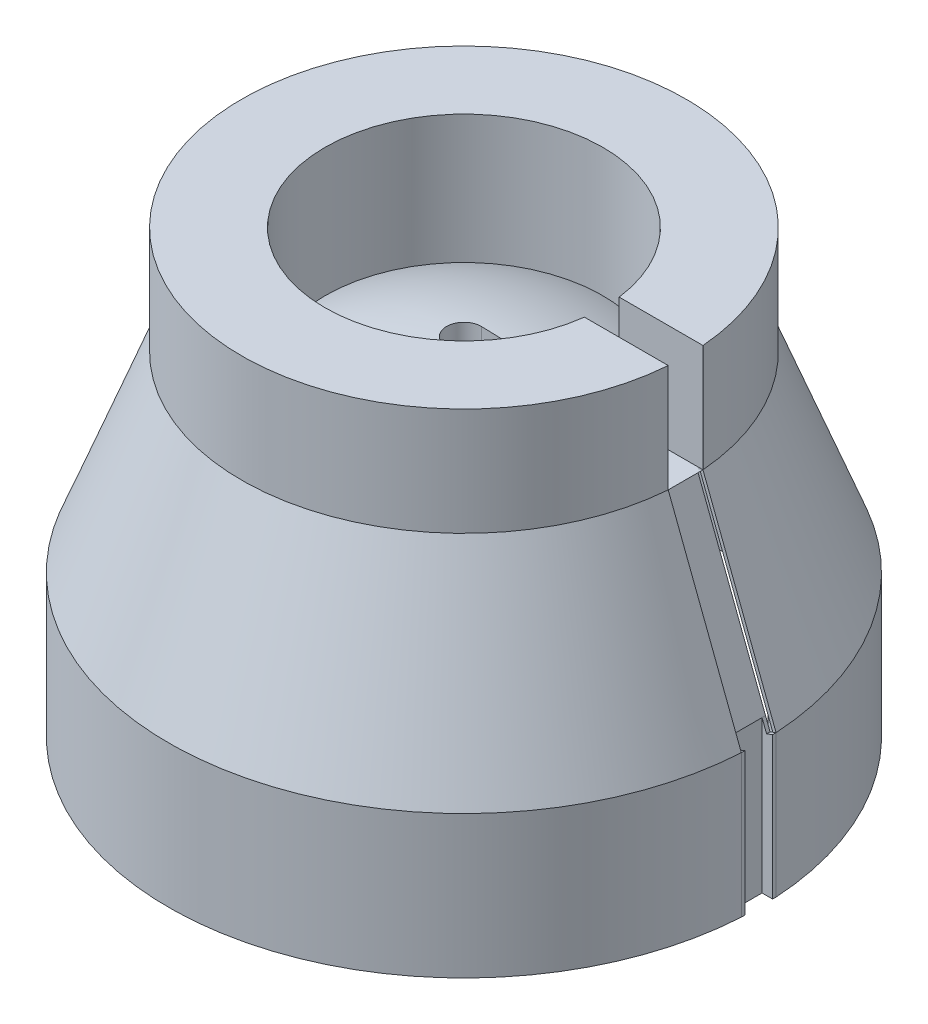
SolidWorks part; units mm, degrees
material "ABS PC"
ref_plane "Front Plane" through (0, 0, 0) normal (0, 0, 1) x (1, 0, 0)
ref_plane "Top Plane" through (0, 0, 0) normal (0, 1, 0) x (1, 0, 0)
ref_plane "Right Plane" through (0, 0, 0) normal (1, 0, 0) x (0, 0, -1)
sketch "Sketch1" plane through (0, 0, 0) normal (0, 0, 1) x (1, 0, 0)
  line L0 (0, 90) -> (0, 0) construction
  line L1 (0, 0) -> (85, 0) construction
  line L2 (85, 0) -> (85, 41)
  line L3 (85, 41) -> (64, 96)
  line L4 (64, 96) -> (64, 127)
  line L5 (64, 127) -> (40, 127)
  line L6 (40, 127) -> (40, 90)
  line L7 (40, 90) -> (0, 90)
  line L8 (84, 0) -> (84, 40.8156)
  line L9 (84, 40.8156) -> (63, 95.8156)
  line L10 (63, 95.8156) -> (63, 126)
  line L11 (63, 126) -> (41, 126)
  line L12 (41, 126) -> (41, 89)
  line L13 (41, 89) -> (0, 89)
  line L14 (0, 90) -> (0, 89)
  line L15 (84, 0) -> (85, 0)
  dimension "D1" = 85
  dimension "D2" = 90
  dimension "D3" = 41
  dimension "D4" = 31
  dimension "D5" = 24
  dimension "D6" = 37
  dimension "D7" = 40
  dimension "D8" = 1
revolve "Revolve1" add sketch "Sketch1" angle 360 about L0
dome "Dome4" faces to dome 1 distance 10 reverse direction no elliptical dome no face at (-40, 90, 0) parameters "D1"=10
sketch "Sketch4" plane through (0, 0, 0) normal (0, 1, 0) x (1, 0, 0)
  circle A0 centre (-75.1149, -19.4222) radius 2.5
  circle A1 centre (-75.1149, -19.4222) radius 5
  dimension "D1" = 10
  dimension "D2" = 5
extrude "Boss-Extrude1" add sketch "Sketch4" along normal blind 45
pattern_circular "CirPattern1" count 4 over 360 about axis through (0, 95.8156, 0) along (0, 1, 0) of "Boss-Extrude1"
sketch "Sketch5" plane through (0, 0, 0) normal (1, 0, 0) x (0, 0, -1)
  line L0 (40, 127) -> (-40, 127) construction
  line L1 (-5, 127) -> (5, 127)
  line L2 (-5, 127) -> (-5, 96)
  line L3 (-5, 96) -> (5, 96)
  line L4 (5, 127) -> (5, 96)
  line L5 (-64, 96) -> (64, 96) construction
  point P8 (0, 96)
  dimension "D1" = 10
extrude "Cut-Extrude2" cut sketch "Sketch5" along normal offset from surface (89.861 mm away) 50 up to face at (-40, 90, 0)
sketch "Sketch6" plane through (0, 0, 5) normal (0, 0, -1) x (-1, 0, 0)
  line L1 (-39.6863, 127) -> (-63.8044, 127)
  line L2 (-39.6863, 127) -> (-39.6863, 96)
  line L3 (-39.6863, 96) -> (-63.8044, 96)
  line L4 (-63.8044, 127) -> (-63.8044, 96)
extrude "Boss-Extrude2" add sketch "Sketch6" against normal blind 0.1
sketch "Sketch7" plane through (0, 0, -5) normal (0, 0, 1) x (1, 0, 0)
  line L1 (39.6863, 127) -> (63.8044, 127)
  line L2 (39.6863, 127) -> (39.6863, 96)
  line L3 (39.6863, 96) -> (63.8044, 96)
  line L4 (63.8044, 127) -> (63.8044, 96)
extrude "Boss-Extrude3" add sketch "Sketch7" against normal blind 0.1
sketch "Sketch8" plane through (0, 0, 0) normal (0, 1, 0) x (1, 0, 0)
  line L1 (39.6863, 5) -> (84.8528, 5)
  line L2 (39.6863, 5) -> (39.6863, -5)
  line L3 (39.6863, -5) -> (84.8528, -5)
  line L4 (84.8528, 5) -> (84.8528, -5)
  circle A0 centre (0, 0) radius 85 construction
  point P7 (39.6863, 0)
extrude "Boss-Extrude5" add sketch "Sketch8" along normal up to surface (96 mm away) separate body up to face at (63.4014, 96, 0)
sketch "Sketch11" plane through (0, 0, -5) normal (0, 0, -1) x (-1, 0, 0)
  line L0 (-39.6863, 67.1394) -> (-75.4269, 0)
  line L1 (-39.6863, 96) -> (-39.6863, 0) construction
  line L2 (-84.8528, 0) -> (-39.6863, 0) construction
  line L3 (-75.4269, 0) -> (-39.6863, 0)
  line L4 (-39.6863, 0) -> (-39.6863, 67.1394)
extrude "Cut-Extrude13" cut sketch "Sketch11" against normal blind 20
sketch "Sketch12" plane through (0, 96, 0) normal (0, 1, 0) x (1, 0, 0)
  line L0 (84.8528, 5) -> (39.6863, 5) construction
  line L1 (81.8158, 5) -> (84.8528, 5)
  line L2 (81.8158, 5) -> (81.8158, -5)
  line L3 (81.8158, -5) -> (84.8528, -5)
  line L4 (84.8528, 5) -> (84.8528, -5)
extrude "Cut-Extrude15" cut sketch "Sketch12" against normal blind 190
sketch "Sketch13" plane through (81.8158, 0, 0) normal (1, 0, 0) x (0, 0, -1)
  line L4 (5, 0) -> (5, 96)
  line L5 (5, 96) -> (-5, 96)
  line L6 (-5, 96) -> (-5, 0)
  line L7 (-5, 0) -> (5, 0)
  line L8 (5, 0) -> (5, 96)
  line L9 (5, 96) -> (-5, 96)
  line L10 (-5, 96) -> (-5, 0)
  line L11 (-5, 0) -> (5, 0)
  dimension "D1" = 0
extrude "Cut-Extrude16" cut sketch "Sketch13" along normal blind 190
sketch "Sketch14" plane through (0, 0, 5) normal (0, 0, -1) x (-1, 0, 0)
  line L0 (-81.8158, 48.9399) -> (-84.8528, 41)
  line L1 (-84.8528, 41) -> (-84.8528, 0)
  line L2 (-84.8528, 0) -> (-81.8158, 0)
  line L3 (-81.8158, 0) -> (-81.8158, 48.9399)
extrude "Boss-Extrude7" add sketch "Sketch14" along normal blind 1 separate body
sketch "Sketch15" plane through (0, 0, -5) normal (0, 0, 1) x (1, 0, 0)
  line L0 (81.8158, 48.9399) -> (84.8528, 41)
  line L1 (84.8528, 41) -> (84.8528, 0)
  line L2 (84.8528, 0) -> (81.8158, 0)
  line L3 (81.8158, 0) -> (81.8158, 48.9399)
extrude "Boss-Extrude9" add sketch "Sketch15" along normal blind 1 separate body
ref_plane "Plane1" through (87.8477, 33.5418, 0) normal (0.9342, 0.3567, 0) x (0, 0, -1)
sketch "Sketch17" plane through (87.8477, 33.5418, 0) normal (0.9342, 0.3567, 0) x (0, 0, -1)
  line L1 (-5, 66.9258) -> (5, 66.9258)
  line L2 (-5, 66.9258) -> (-5, 8.0358)
  line L3 (-5, 8.0358) -> (5, 8.0358)
  line L4 (5, 66.9258) -> (5, 8.0358)
extrude "Cut-Extrude17" cut sketch "Sketch17" against normal blind 2 and the other way blind 31
sketch "Sketch18" plane through (0, 89, 0) normal (0, -1, 0) x (1, 0, 0)
  circle A0 centre (0, 0) radius 5
  dimension "D1" = 10
extrude "Cut-Extrude18" cut sketch "Sketch18" against normal blind 42
sketch "Sketch19" plane through (0, 89, 0) normal (0, -1, 0) x (1, 0, 0)
  circle A0 centre (0, 0) radius 33.3812
  circle A1 centre (0, 0) radius 30.2782
extrude "Boss-Extrude10" add sketch "Sketch19" along normal blind 5
fillet "Fillet2" radius 1 2 edges at (30.2782, 84, 0) (33.3812, 84, 0)
